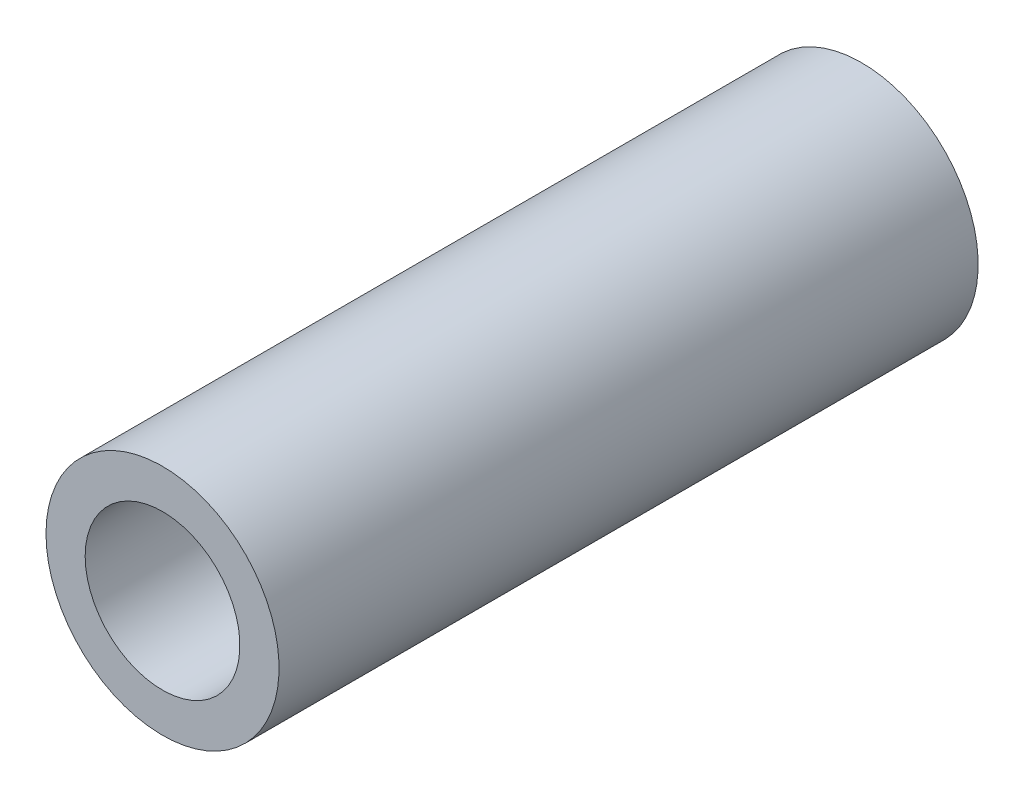
SolidWorks part; units mm, degrees
ref_plane "Front Plane" through (0, 0, 0) normal (0, 0, 1) x (1, 0, 0)
ref_plane "Top Plane" through (0, 0, 0) normal (0, 1, 0) x (1, 0, 0)
ref_plane "Right Plane" through (0, 0, 0) normal (1, 0, 0) x (0, 0, -1)
sketch "Sketch1" plane through (0, 0, 0) normal (0, 0, 1) x (1, 0, 0)
  circle A0 centre (0, 0) radius 3.175
  circle A1 centre (0, 0) radius 2.1082
  dimension "OD" = 6.35
  dimension "ID" = 4.2164
extrude "Extrude1" add sketch "Sketch1" along normal mid plane 19.05
sketch "Sketch2" plane through (0, 0, 0) normal (1, 0, 0) x (0, 0, -1)
  line L0 (-9.525, -2.1082) -> (9.525, -2.1082) construction
  line L3 (9.525, 2.1082) -> (-9.525, 2.1082) construction
  line L5 (-9.525, -2.1082) -> (9.525, -2.1082)
  line L6 (9.525, 2.1082) -> (-9.525, 2.1082)
sketch "Sketch4" plane through (0, 0, 9.525) normal (0, 0, 1) x (1, 0, 0)
  line L0 (0, 0) -> (-1.4907, 1.4907)
  line L1 (0, -3.4925) -> (0, 3.4925) construction
  circle A0 centre (0, 0) radius 2.1082 construction
  dimension "D1" = 45
